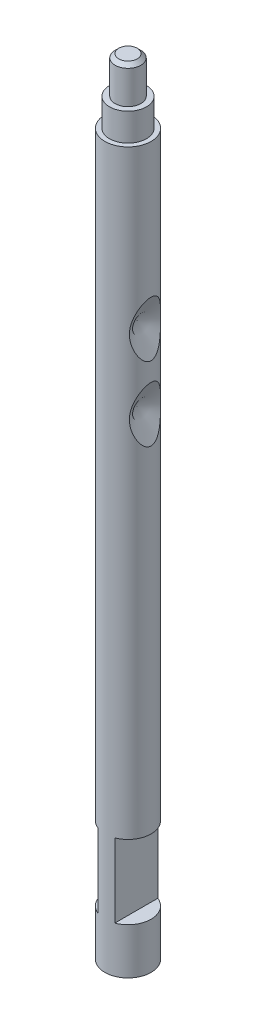
SolidWorks part; units mm, degrees
ref_plane "Front Plane" through (0, 0, 0) normal (0, 0, 1) x (1, 0, 0)
ref_plane "Top Plane" through (0, 0, 0) normal (0, 1, 0) x (1, 0, 0)
ref_plane "Right Plane" through (0, 0, 0) normal (1, 0, 0) x (0, 0, -1)
sketch "Sketch1" plane through (0, 0, 0) normal (0, 1, 0) x (1, 0, 0)
  circle A0 centre (0, 0) radius 1.25
  dimension "D1" = 2.5
extrude "Boss-Extrude1" add sketch "Sketch1" along normal blind 42.5
sketch "Sketch2" plane through (0, 42.5, 0) normal (0, 1, 0) x (1, 0, 0)
  circle A0 centre (0, 0) radius 1
  dimension "D1" = 2
extrude "Cut-Extrude1" cut sketch "Sketch2" against normal blind 3.5 flip side to cut
sketch "Sketch3" plane through (0, 42.5, 0) normal (0, 1, 0) x (1, 0, 0)
  circle A0 centre (0, 0) radius 0.7
  dimension "D1" = 1.4
extrude "Cut-Extrude2" cut sketch "Sketch3" against normal blind 2 flip side to cut
cosmetic thread "Cosmetic Thread1" parameters "D2"=1.057
chamfer "Chamfer1" distance 0.2 angle 45 1 edges at (0, 42.5, 0.7)
sketch "Sketch4" plane through (0, 0, 0) normal (0, 0, 1) x (1, 0, 0)
  line L0 (0, 0) -> (0, 15.8008) construction
  line L1 (-1.25, 0) -> (1.25, 0) construction
  line L2 (0.45, 6.5) -> (1.25, 6.5)
  line L3 (0.45, 6.5) -> (0.45, 2.5)
  line L4 (0.45, 2.5) -> (1.25, 2.5)
  line L5 (-1.25, 2.5) -> (-1.25, 6.5)
  line L6 (-0.45, 2.5) -> (-1.25, 2.5)
  line L7 (-0.45, 6.5) -> (-0.45, 2.5)
  line L8 (-0.45, 6.5) -> (-1.25, 6.5)
  line L9 (1.25, 0) -> (1.25, 39) construction
  line L10 (1.25, 2.5) -> (1.25, 6.5)
  dimension "D1" = 0.9
  dimension "D2" = 2.5
  dimension "D3" = 4
extrude "Cut-Extrude3" cut sketch "Sketch4" against normal through all both and the other way through all
sketch "Sketch5" plane through (0, 0, 0) normal (0, 0, 1) x (1, 0, 0)
  line L0 (0, 42.5) -> (0, 28.4235) construction
  line L1 (0.5, 42.5) -> (-0.5, 42.5) construction
  line L2 (1.25, 31.6916) -> (0.49, 30.2)
  line L3 (1.25, 6.5) -> (1.25, 39) construction
  line L4 (0.49, 30.2) -> (1.25, 28.7084) construction
  line L5 (0.49, 30.2) -> (1.8893, 30.2) construction
  line L6 (1.25, 30.2) -> (1.25, 31.6916)
  line L7 (0.49, 30.2) -> (1.25, 30.2)
  dimension "D1" = 126
  dimension "D2" = 0.98
  dimension "D3" = 8.8
revolve "Cut-Revolve2" cut sketch "Sketch5" angle 360 about L5
pattern_linear "LPattern1" count 2 spacing 4 along (0, -1, 0) of "Cut-Revolve2"
